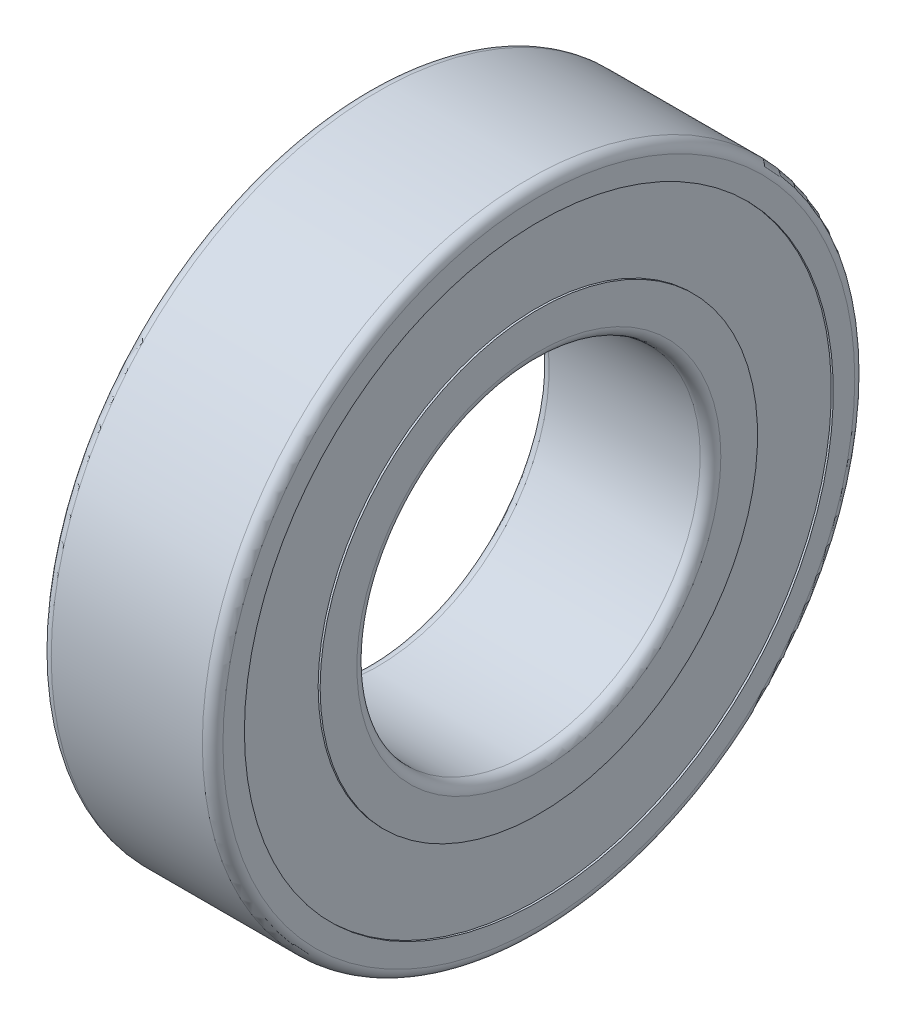
SolidWorks part; units mm, degrees
material "1.4301 (X5CrNi18-10)"
ref_plane "正面" through (0, 0, 0) normal (0, 0, 1) x (1, 0, 0)
ref_plane "平面" through (0, 0, 0) normal (0, 1, 0) x (1, 0, 0)
ref_plane "右側面" through (0, 0, 0) normal (1, 0, 0) x (0, 0, -1)
sketch "ｽｹｯﾁ1" plane through (0, 0, 0) normal (0, 0, 1) x (1, 0, 0)
  line L0 (0, 0) -> (9122.5862, 0) construction
  line L3 (0, 9.5) -> (-5, 9.5)
  line L4 (-5, 9.5) -> (-5, 8.575)
  line L5 (-4.7425, 8.4225) -> (-3.3124, 8.4225)
  line L6 (0, 8.575) -> (0, 9.5)
  line L7 (-4.7425, 6.5225) -> (-3.3124, 6.5225)
  line L8 (0, 6.37) -> (0, 5)
  line L9 (0, 5) -> (-5, 5)
  line L10 (-5, 5) -> (-5, 6.37)
  line L11 (0, 6.37) -> (-0.2575, 6.37)
  line L12 (-0.2575, 6.37) -> (-0.2575, 6.5225)
  line L13 (-0.2575, 8.575) -> (0, 8.575)
  line L14 (-5, 8.575) -> (-4.7425, 8.575)
  line L15 (-4.7425, 8.575) -> (-4.7425, 8.4225)
  line L16 (-4.7425, 6.37) -> (-5, 6.37)
  line L17 (-4.7425, 6.5225) -> (-4.7425, 6.37)
  line L18 (-0.2575, 8.4225) -> (-0.2575, 8.575)
  line L19 (-5, 7.4725) -> (0, 7.4725) construction
  line L20 (-2.5, 5) -> (-2.5, 9.5) construction
  line L21 (-1.6876, 8.4225) -> (-0.2575, 8.4225)
  line L22 (-4.7425, 6.37) -> (-4.9425, 6.37)
  line L23 (-4.7425, 6.37) -> (-4.7425, 8.575)
  line L24 (-4.7425, 8.575) -> (-4.9425, 8.575)
  line L25 (-4.9425, 6.37) -> (-4.9425, 8.575)
  line L26 (-0.2575, 6.37) -> (-0.0575, 6.37)
  line L27 (-0.2575, 6.37) -> (-0.2575, 8.575)
  line L28 (-0.2575, 8.575) -> (-0.0575, 8.575)
  line L29 (-0.0575, 6.37) -> (-0.0575, 8.575)
  line L30 (-1.6876, 6.5225) -> (-0.2575, 6.5225)
  line L31 (-3.75, 7.4725) -> (-1.25, 7.4725)
  circle A1 centre (-2.5, 7.4725) radius 1.25 construction
  arc A2 (-3.3124, 8.4225) -> (-1.6876, 8.4225) centre (-2.5, 7.4725) cw
  arc A3 (-3.3124, 6.5225) -> (-1.6876, 6.5225) centre (-2.5, 7.4725) ccw
  arc A4 (-3.75, 7.4725) -> (-1.25, 7.4725) centre (-2.5, 7.4725) cw
  dimension "D1" = 5
  dimension "D10" = 2.5
  dimension "D12" = 0.2
  dimension "D2" = 10
  dimension "D3" = 12.74
  dimension "D4" = 17.15
  dimension "D6" = 19
  dimension "D9" = 0.0575
  dimension "D11" = 0.3
revolve "回転1" add sketch "ｽｹｯﾁ1" angle 360 about L0 region at (-2.5, 8.9965, 0) region at (-2.5, 5.7241, 0)
revolve "回転3" add sketch "ｽｹｯﾁ1<4>" angle 360 about L19 region at (-2.5, 8.003, 0)
sketch "ｽｹｯﾁ1<4>" plane through (0, 0, 0) normal (0, 0, 1) x (1, 0, 0) same geometry as "ｽｹｯﾁ1"
pattern_circular "円形ﾊﾟﾀｰﾝ5" count 10 over 360 about axis through (0, 0, 0) along (-1, 0, 0) of bodies 105
revolve "回転2" add sketch "ｽｹｯﾁ1<3>" angle 360 about L0 region at (-0.1575, 7.4725, 0) region at (-4.8425, 7.4725, 0)
sketch "ｽｹｯﾁ1<3>" plane through (0, 0, 0) normal (0, 0, 1) x (1, 0, 0) same geometry as "ｽｹｯﾁ1"
fillet "ﾌｨﾚｯﾄ1" radius 0.3 2 edges at (0, 0, 5) (-5, 0, 5)
fillet "ﾌｨﾚｯﾄ2" radius 0.3 2 edges at (-5, 0, 9.5) (0, 0, 9.5)
